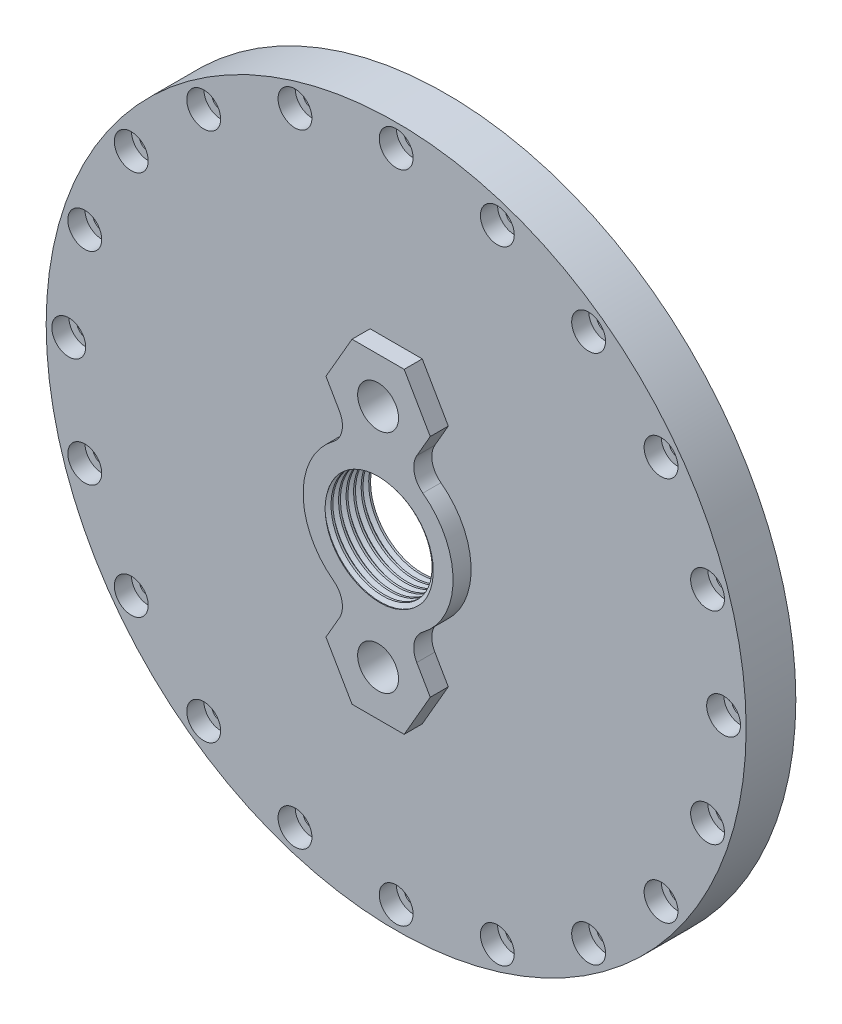
SolidWorks part; units mm, degrees
ref_plane "Front Plane" through (0, 0, 0) normal (0, 0, 1) x (1, 0, 0)
ref_plane "Top Plane" through (0, 0, 0) normal (0, 1, 0) x (1, 0, 0)
ref_plane "Right Plane" through (0, 0, 0) normal (1, 0, 0) x (0, 0, -1)
sketch "Sketch1" plane through (0, 0, 0) normal (1, 0, 0) x (0, 0, -1)
  line L0 (0, 21.082) -> (0, 98.425)
  line L1 (0, 98.425) -> (13.97, 98.425)
  line L2 (13.97, 98.425) -> (13.97, 81.6627)
  line L3 (13.97, 81.6627) -> (5.08, 81.6627)
  line L4 (5.08, 81.6627) -> (5.08, 55.245)
  line L5 (5.08, 55.245) -> (7.62, 55.245)
  line L6 (7.62, 55.245) -> (7.62, 50.165)
  line L7 (7.62, 14.732) -> (-5.08, 14.732)
  line L8 (-5.08, 14.732) -> (-5.08, 21.082)
  line L9 (-5.08, 21.082) -> (0, 21.082)
  line L10 (0, 0) -> (59.2702, 0) construction
  line L12 (7.62, 50.165) -> (6.35, 50.165)
  line L14 (7.62, 48.895) -> (6.35, 48.895)
  line L15 (6.35, 50.165) -> (6.35, 48.895)
  line L20 (7.62, 48.895) -> (7.62, 47.625)
  line L21 (13.97, 81.6627) -> (13.97, 81.4626) construction
  line L22 (13.97, 81.6627) -> (13.97, 81.4626) construction
  line L23 (7.62, 21.59) -> (7.62, 14.732)
  line L24 (7.62, 47.625) -> (5.08, 47.625)
  line L26 (7.62, 21.59) -> (5.08, 21.59)
  line L27 (5.08, 47.625) -> (5.08, 21.59)
  point P22 (6.35, 49.53)
  dimension "D1" = 196.85
  dimension "D2" = 2.54
  dimension "D3" = 13.97
  dimension "D4" = 2.54
  dimension "D5" = 110.49
  dimension "D6" = 12.7
  dimension "D7" = 29.464
  dimension "D8" = 6.35
  dimension "D9" = 1.27
  dimension "D10" = 99.06
  dimension "D11" = 1.27
  dimension "D12" = 6.35
  dimension "D13" = 95.25
  dimension "D14" = 43.18
revolve "Revolve1" add sketch "Sketch1" angle 360 about L10 region at (0, 61.2264, -4.1141)
thread "Thread1" pitch 2.1167 method cut profile "Thread Profile1" start angle 0, offset 4.318, length 0, pitch 2.1167, diameter 29.464
ref_plane "Plane1" through (-14.732, 0, 9.398) normal (0, -1, 0) x (-1, 0, 0)
sketch "Thread Profile1" plane through (-14.732, 0, 9.398) normal (0, -1, 0) x (-1, 0, 0)
  line L0 (0, 0) -> (0, 2.1167) construction
  line L1 (0, 0) -> (1.1457, 0.6615)
  line L2 (1.1457, 0.6615) -> (1.1457, 0.926)
  line L3 (1.1457, 0.926) -> (0, 1.5875)
  line L4 (1.1457, 0.7937) -> (0, 0.7937) construction
  line L11 (0, 0) -> (0, 1.5875)
  point P2 (0, 0)
  dimension "Pitch" = 2.1167
  dimension "Profile_Angle" = 60
  dimension "Profile_Land" = 0.2646
  dimension "Profile_Height" = 1.1457
sketch "Sketch15" plane through (0, 0, 0) normal (0, 0, 1) x (1, 0, 0)
  line L10 (0, 0) -> (104.8126, 0) construction
  line L11 (7.3323, 19.05) -> (14.6647, 31.75)
  line L12 (14.6647, 31.75) -> (7.3323, 44.45)
  line L13 (7.3323, 44.45) -> (-7.3323, 44.45)
  line L14 (-7.3323, 44.45) -> (-14.6647, 31.75)
  line L15 (-14.6647, 31.75) -> (-7.3323, 19.05)
  line L16 (-7.3323, 19.05) -> (7.3323, 19.05)
  line L17 (-7.3323, -19.05) -> (7.3323, -19.05)
  line L18 (-14.6647, -31.75) -> (-7.3323, -19.05)
  line L19 (-7.3323, -44.45) -> (-14.6647, -31.75)
  line L20 (7.3323, -44.45) -> (-7.3323, -44.45)
  line L21 (14.6647, -31.75) -> (7.3323, -44.45)
  line L22 (7.3323, -19.05) -> (14.6647, -31.75)
  circle A8 centre (0, 31.75) radius 12.7 construction
  circle A9 centre (0, -31.75) radius 12.7 construction
  dimension "D2" = 63.5
  dimension "D1" = 25.4
extrude "Boss-Extrude1" add sketch "Sketch15" along normal up to surface (5.08 mm away) up to face at (21.082, 0, 5.08)
hole_wizard "1/2-20 Tapped Hole2" positions "Sketch20" profile "Sketch17" tap size "1/2-20" standard "ANSI Inch" end condition through all
sketch "Sketch20" plane through (0, 0, 5.08) normal (0, 0, 1) x (1, 0, 0)
  point P9 (0, 31.75)
  point P16 (0, -31.75)
sketch "Sketch17" plane through (0, 31.75, 5.08) normal (1, 0, 0) x (0, -1, 0)
  line L0 (0, 0) -> (0, 19.05)
  line L1 (0, 19.05) -> (5.7544, 19.05)
  line L2 (5.7544, 19.05) -> (5.7544, 0)
  line L5 (5.7544, 0) -> (0, 0)
  line L11 (0, -6.35) -> (0, 107.95) construction
  dimension "Thru Tap Drill Dia." = 11.5087
  dimension "Thru Tap Drill Depth" = 19.05
cosmetic thread "Hole Thread3" parameters "D2"=12.7
cosmetic thread "Hole Thread4" parameters "D2"=12.7
hole_wizard "CBORE for #10 Socket Head Cap Screw1" positions "Sketch19" profile "Sketch9" counterbore size "#10" standard "ANSI Inch" end condition up to next
sketch "Sketch19" plane through (0, 0, 0) normal (0, 0, 1) x (1, 0, 0)
  circle A0 centre (0, 0) radius 92.075 construction
  point P0 (0, 92.075)
  point P16 (28.4527, 87.5685)
  point P17 (54.1203, 74.4902)
  point P18 (74.4902, 54.1203)
  point P19 (87.5685, 28.4527)
  point P20 (92.075, 0)
  point P21 (87.5685, -28.4527)
  point P22 (74.4902, -54.1203)
  point P23 (54.1203, -74.4902)
  point P24 (28.4527, -87.5685)
  point P25 (0, -92.075)
  point P26 (-28.4527, -87.5685)
  point P27 (-54.1203, -74.4902)
  point P28 (-74.4902, -54.1203)
  point P29 (-87.5685, -28.4527)
  point P30 (-92.075, 0)
  point P31 (-87.5685, 28.4527)
  point P32 (-74.4902, 54.1203)
  point P33 (-54.1203, 74.4902)
  point P34 (-28.4527, 87.5685)
  dimension "D1" = 184.15
  dimension "D2" = 20
sketch "Sketch9" plane through (0, 92.075, 0) normal (1, 0, 0) x (0, -1, 0)
  line L0 (0, 0) -> (0, 13.97)
  line L1 (0, 13.97) -> (2.5527, 13.97)
  line L3 (2.5527, 13.97) -> (2.5527, 4.826)
  line L4 (2.5527, 4.826) -> (4.7625, 4.826)
  line L5 (4.7625, 4.826) -> (4.7625, 0)
  line L7 (4.7625, 0) -> (0, 0)
  line L11 (0, -6.35) -> (0, 107.95) construction
  dimension "Thru Hole Dia." = 5.1054
  dimension "Thru Hole Depth" = 13.97
  dimension "C'Bore Dia." = 9.525
  dimension "C'Bore Depth" = 4.826
fillet "Fillet1" radius 6.35 4 edges at (-7.6711, 19.6368, 2.54) (-7.6711, -19.6368, 2.54) (7.6711, -19.6368, 2.54) (7.6711, 19.6368, 2.54)
